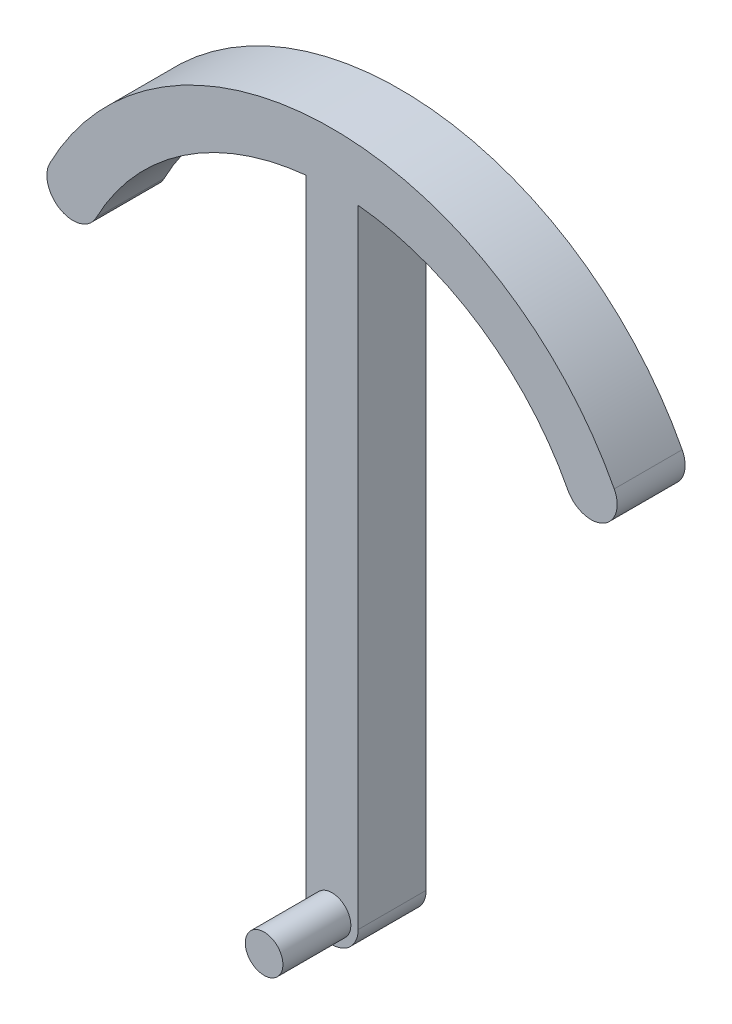
SolidWorks part; units mm, degrees
ref_plane "Front Plane" through (0, 0, 0) normal (0, 0, 1) x (1, 0, 0)
ref_plane "Top Plane" through (0, 0, 0) normal (0, 1, 0) x (1, 0, 0)
ref_plane "Right Plane" through (0, 0, 0) normal (1, 0, 0) x (0, 0, -1)
sketch "Sketch1" plane through (0, 0, 0) normal (0, 0, 1) x (1, 0, 0)
  line L0 (-3.175, 0) -> (-3.175, 76.2)
  line L1 (3.175, 0) -> (3.175, 76.2)
  line L2 (0, 0) -> (0, -50000) construction
  line L3 (0, 0) -> (-23087.4307, 44350.5417) construction
  line L4 (0, 0) -> (23087.4307, 44350.5417) construction
  arc A0 (3.175, 0) -> (-3.175, 0) centre (0, 0) cw
  arc A1 (-3.175, 76.2) -> (-28.6519, 58.9807) centre (0, 44.0455) ccw
  arc A2 (-28.6519, 58.9807) -> (-34.2828, 61.9159) centre (-31.4674, 60.4483) cw
  arc A3 (-34.2828, 61.9159) -> (34.2828, 61.9159) centre (0, 44.0455) cw
  arc A4 (28.6519, 58.9807) -> (34.2828, 61.9159) centre (31.4674, 60.4483) ccw
  arc A5 (3.175, 76.2) -> (28.6519, 58.9807) centre (0, 44.0455) cw
  dimension "D1" = 55
  dimension "D2" = 6.35
  dimension "D3" = 76.2
  dimension "D4" = 6.35
extrude "Boss-Extrude1" add sketch "Sketch1" along normal blind 8.255
sketch "Sketch2" plane through (0, 0, 8.255) normal (0, 0, 1) x (1, 0, 0)
  circle A0 centre (0, 0) radius 2.286
  dimension "D1" = 4.572
extrude "Boss-Extrude2" add sketch "Sketch2" along normal blind 8.255
equation "\"slot-width\"=0.1"
equation "\"slot-end-angle\"=60"
equation "\"slot-spacing-angle\"=60"
equation "\"slot-gap\"=0.01"
equation "\"pin-diameter\"=2*\"slot-width\"-2*\"slot-gap\""
equation "\"D1@Sketch2\"=\"pin-diameter\""
equation "\"pulley-thickness\"=0.25"
